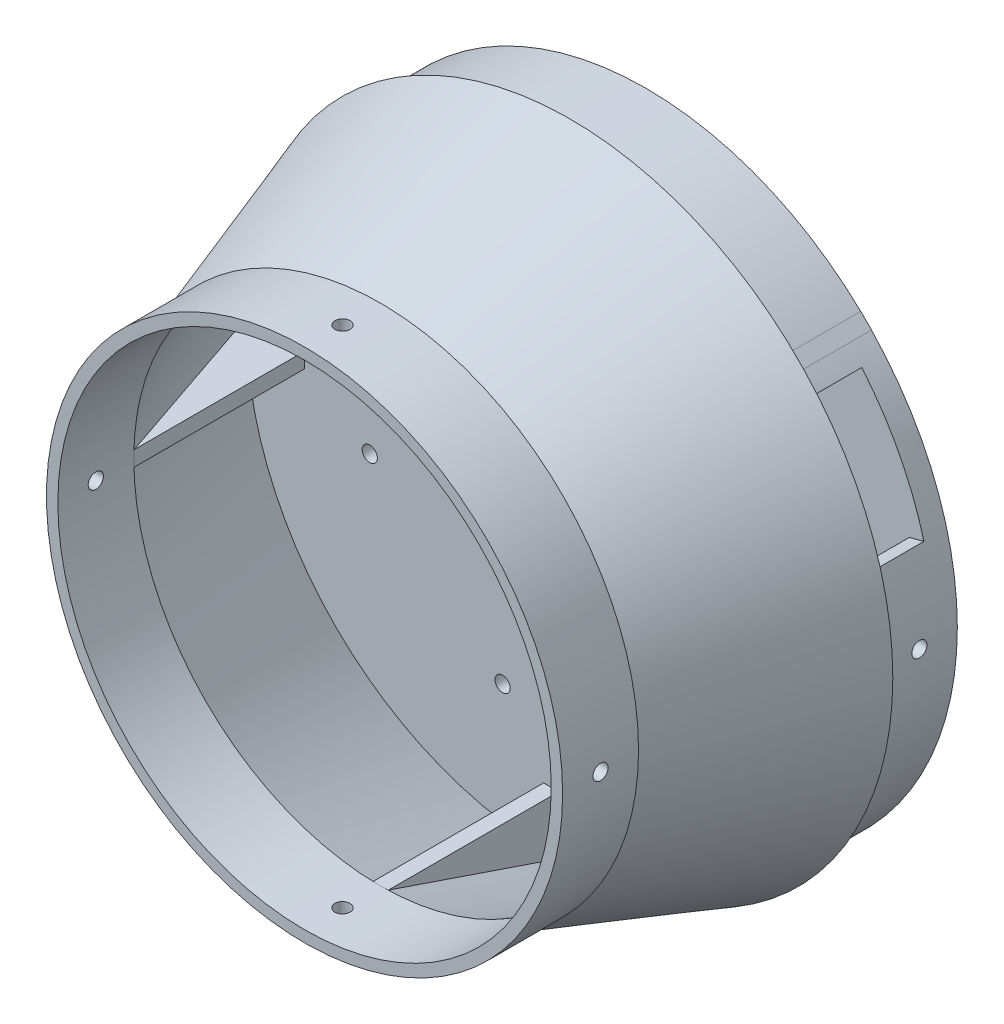
SolidWorks part; units mm, degrees
ref_plane "Front Plane" through (0, 0, 0) normal (0, 0, 1) x (1, 0, 0)
ref_plane "Top Plane" through (0, 0, 0) normal (0, 1, 0) x (1, 0, 0)
ref_plane "Right Plane" through (0, 0, 0) normal (1, 0, 0) x (0, 0, -1)
sketch "Sketch10" plane through (0, 0, 0) normal (0, 1, 0) x (1, 0, 0)
  line L9 (68, 0) -> (85, 50)
  line L10 (65, 0) -> (65, -20)
  line L11 (65, -20) -> (68, -20)
  line L12 (68, -20) -> (68, 0)
  line L13 (85, 50) -> (0, 50)
  line L14 (0, 50) -> (0, 45)
  line L16 (0, 0) -> (0, 90.5218) construction
  line L17 (65, 0) -> (80.3, 45)
  line L18 (0, 45) -> (80.3, 45)
  dimension "D1" = 65
  dimension "D2" = 20
  dimension "D3" = 50
  dimension "D4" = 85
  dimension "D5" = 68
  dimension "D6" = 5
revolve "Revolve2" add sketch "Sketch10" angle 360 about L16
sketch "Sketch12" plane through (0, 0, 0) normal (0, 1, 0) x (1, 0, 0)
  line L4 (-80.3, 45) -> (-65, 0)
  line L5 (-65, 0) -> (-65, 45)
  line L6 (-80.3, 45) -> (80.3, 45) construction
  line L7 (-65, 45) -> (-80.3, 45)
extrude "Boss-Extrude5" add sketch "Sketch12" along normal blind 2 and the other way blind 2
pattern_circular "CirPattern3" count 4 every 90 about axis through (0, 0, -50) along (0, 0, 1) of "Boss-Extrude5"
sketch "Sketch13" plane through (0, 0, -50) normal (0, 0, -1) x (-1, 0, 0)
  arc A0 (70, 42.7083) -> (70, -42.7083) centre (0, 0) ccw
  arc A1 (70, 34.4093) -> (70, -34.4093) centre (0, 0) ccw
  circle A2 centre (0, 0) radius 82 construction
  circle A3 centre (0, 0) radius 78 construction
  circle A4 centre (0, 0) radius 82
  circle A5 centre (0, 0) radius 78
  dimension "D1" = 164
  dimension "D2" = 4
extrude "Boss-Extrude6" add sketch "Sketch13" along normal blind 20 contours A0 A4 A5 A1 region at (-76.7102, 21.5537, -50)
sketch "Sketch14" plane through (0, 0, 0) normal (0, 1, 0) x (1, 0, 0)
  line L0 (-65, -20) -> (65, -20) construction
  circle A0 centre (0, -10) radius 2
  dimension "D1" = 4
  dimension "D2" = 10
extrude "Cut-Extrude1" cut sketch "Sketch14" against normal blind 95
pattern_circular "CirPattern4" count 4 every 90 about axis through (0, 0, 20) along (0, 0, 1) of "Cut-Extrude1"
fillet "Fillet1" radius 5 1 edges at (-78, 0, -50)
sketch "Sketch16" plane through (0, 0, 0) normal (0, 1, 0) x (1, 0, 0)
  line L0 (85, 50) -> (-85, 50) construction
  circle A0 centre (0, 60) radius 2
  dimension "D1" = 4
  dimension "D2" = 10
extrude "Cut-Extrude2" cut sketch "Sketch16" against normal blind 94
pattern_circular "CirPattern5" count 2 every 90 about axis through (0, 0, -70) along (0, 0, -1) of "Cut-Extrude2" other way count 2
sketch "Sketch17" plane through (0, 0, -50) normal (0, 0, -1) x (-1, 0, 0)
  line L0 (0, 0) -> (-47.8133, 12.8115) construction
  line L1 (0, 0) -> (-12.8115, 47.8133) construction
  circle A0 centre (-47.8133, 12.8115) radius 2
  circle A4 centre (-12.8115, 47.8133) radius 2
  circle A5 centre (12.8115, -47.8133) radius 2
  circle A6 centre (47.8133, -12.8115) radius 2
  point P12 (0, 0)
  point P16 (0, 0)
  dimension "D1" = 4
  dimension "D2" = 49.5
  dimension "D4" = 60
  dimension "D3" = 2
  dimension "D5" = 2
extrude "Cut-Extrude4" cut sketch "Sketch17" against normal blind 900
sketch "Sketch19" plane through (0, 0, -70) normal (0, 0, -1) x (-1, 0, 0)
  line L0 (0, 0) -> (0, 85) construction
  line L1 (0, 0) -> (-79.2059, 21.2232)
  line L6 (0, 0) -> (-62.8156, 52.7086)
  circle A0 centre (0, 0) radius 85 construction
  arc A2 (-62.8156, 52.7086) -> (-79.2059, 21.2232) centre (0, 0) ccw
  dimension "D1" = 75
  dimension "D2" = 50
extrude "Cut-Extrude7" cut sketch "Sketch19" against normal blind 20
mirror "Mirror1" about plane through (0, 0, 0) normal (1, 0, 0) of "Cut-Extrude7"
sketch "Sketch22" plane through (0, 0, -70) normal (0, 0, -1) x (-1, 0, 0)
  circle A2 centre (0, 0) radius 82
  circle A3 centre (0, 0) radius 60
  arc M2 (-59.7515, 50.1374) -> (59.7515, 50.1374) centre (0, 0) cw
  line M3 (59.7515, 50.1374) -> (62.8156, 52.7086)
  arc M4 (62.8156, 52.7086) -> (-62.8156, 52.7086) centre (0, 0) ccw
  line M5 (-62.8156, 52.7086) -> (-59.7515, 50.1374)
  dimension "D1" = 120
extrude "Boss-Extrude8" add sketch "Sketch22" against normal blind 6 contours A2 A3 M5 M3 M2 | M5 M2 M3 M4 region at (27.262, -74.9018, -70) region at (-60.4504, 52.4159, -70)
sketch "Sketch24" plane through (0, 0, -50) normal (0, 0, -1) x (-1, 0, 0)
  circle A0 centre (0, 0) radius 25
  dimension "D1" = 50
extrude "Cut-Extrude8" cut sketch "Sketch24" against normal blind 5
ref_plane "Plane1" through (0, 0, 0) normal (-0.7071, 0.7071, 0) x (0.7071, 0.7071, 0)
sketch "Sketch28" plane through (0, 0, 0) normal (-0.7071, 0.7071, 0) x (0.7071, 0.7071, 0)
  line L0 (-68, 50) -> (-68, 70)
  line L1 (82, 70) -> (-82, 70) construction
  line L2 (-68, 70) -> (-82, 70)
  line L3 (-82, 70) -> (-82, 50)
  line L4 (85, 50) -> (-85, 50) construction
  line L5 (-82, 70) -> (-82, 50) construction
  line L6 (-82, 50) -> (-68, 50)
extrude "Boss-Extrude9" add sketch "Sketch28" along normal blind 2 and the other way blind 2
pattern_circular "CirPattern6" count 4 every 90 about axis through (0, 0, -70) along (0, 0, -1) of "Boss-Extrude9"
